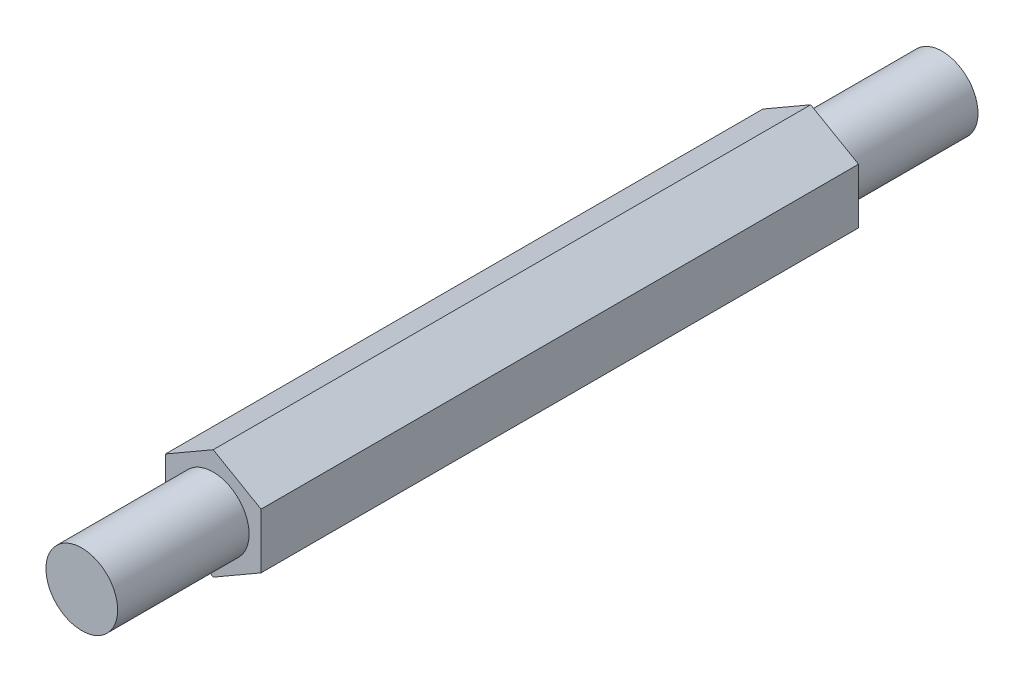
SolidWorks part; units mm, degrees
ref_plane "Front Plane" through (0, 0, 0) normal (0, 0, 1) x (1, 0, 0)
ref_plane "Top Plane" through (0, 0, 0) normal (0, 1, 0) x (1, 0, 0)
ref_plane "Right Plane" through (0, 0, 0) normal (1, 0, 0) x (0, 0, -1)
sketch "Sketch1" plane through (0, 0, 0) normal (0, 0, 1) x (1, 0, 0)
  line L1 (0, -14.6647) -> (12.7, -7.3323)
  line L2 (12.7, -7.3323) -> (12.7, 7.3323)
  line L3 (12.7, 7.3323) -> (0, 14.6647)
  line L4 (0, 14.6647) -> (-12.7, 7.3323)
  line L5 (-12.7, 7.3323) -> (-12.7, -7.3323)
  line L6 (-12.7, -7.3323) -> (0, -14.6647)
  circle A0 centre (0, 0) radius 12.7 construction
  circle A1 centre (0, 0) radius 9.525
  dimension "D2" = 19.05
  dimension "D1" = 25.4
extrude "Boss-Extrude1" add sketch "Sketch1" along normal mid plane 158.75 contours A1 | L5 L6 L1 L2 L3 L4 A1 region at (-6.156, -10.6625, 0) region at (0, 0, 0)
extrude "Boss-Extrude2" add sketch "Sketch1<3>" along normal mid plane 228.6 contours A1 region at (0, 0, 0)
sketch "Sketch1<3>" plane through (0, 0, 0) normal (0, 0, 1) x (1, 0, 0) same geometry as "Sketch1"
